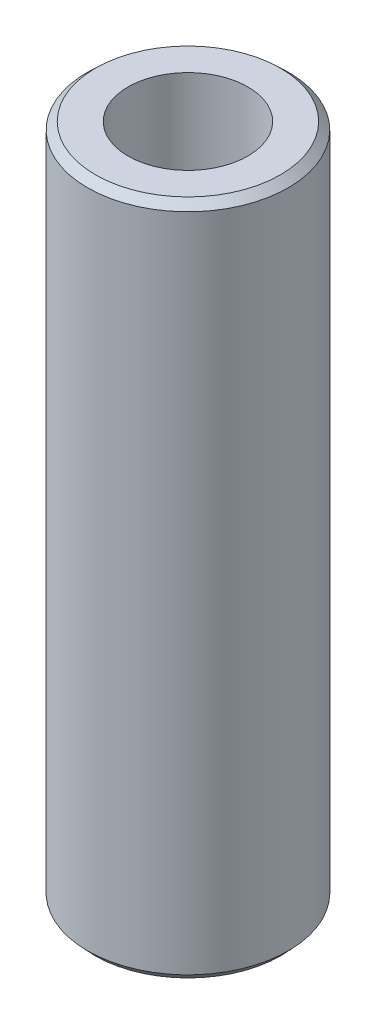
SolidWorks part; units mm, degrees
ref_plane "Front Plane" through (0, 0, 0) normal (0, 0, 1) x (1, 0, 0)
ref_plane "Top Plane" through (0, 0, 0) normal (0, 1, 0) x (1, 0, 0)
ref_plane "Right Plane" through (0, 0, 0) normal (1, 0, 0) x (0, 0, -1)
sketch "Sketch1" plane through (0, 0, 0) normal (0, 1, 0) x (1, 0, 0)
  circle A0 centre (0, 0) radius 27.5
  dimension "SHAFT_OD" = 55
extrude "Boss-Extrude1" add sketch "Sketch1" along normal blind 185.361
sketch "Sketch2" plane through (0, 0, 0) normal (0, 1, 0) x (1, 0, 0)
  circle A0 centre (0, 0) radius 16.4335
  dimension "BORE_D" = 32.8669
extrude "Cut-Extrude1" cut sketch "Sketch2" along normal through all
chamfer "Chamfer1" distance 2.006 angle 47.029 2 edges at (0, 185.361, 27.5) (0, 0, 27.5) first distance on face at (0, 185.361, 27.5) first distance on face at (0, 0, 16.4335)
